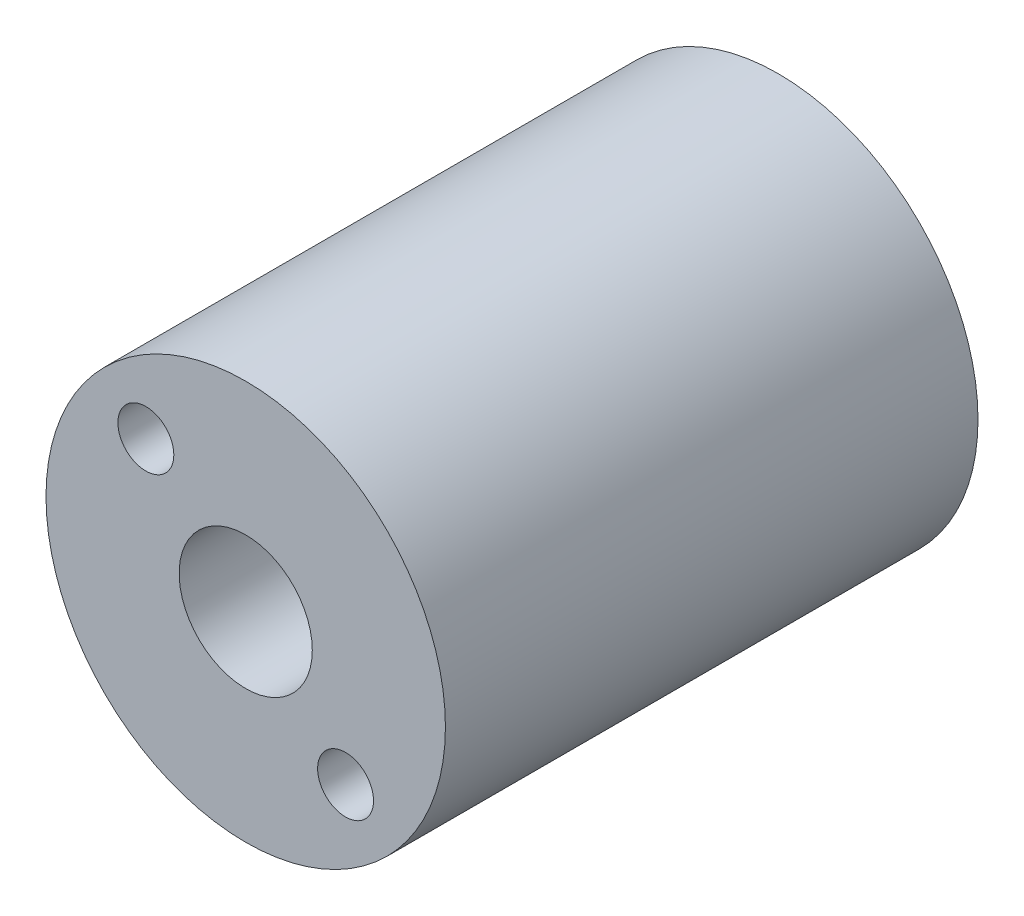
SolidWorks part; units mm, degrees
ref_plane "Ebene vorne" through (0, 0, 0) normal (0, 0, 1) x (1, 0, 0)
ref_plane "Ebene oben" through (0, 0, 0) normal (0, 1, 0) x (1, 0, 0)
ref_plane "Ebene rechts" through (0, 0, 0) normal (1, 0, 0) x (0, 0, -1)
sketch "Skizze1" plane through (0, 0, 0) normal (0, 0, 1) x (1, 0, 0)
  circle A0 centre (0, 0) radius 15
  dimension "D1" = 30
extrude "Aufsatz-Linear austragen1" add sketch "Skizze1" along normal blind 40
sketch "Skizze2" plane through (0, 0, 40) normal (0, 0, 1) x (1, 0, 0)
  circle A0 centre (0, 0) radius 5
  dimension "D1" = 10
extrude "Schnitt-Linear austragen1" cut sketch "Skizze2" against normal through all
hole_wizard "M5 Gewindebohrung1" positions "Skizze7" profile "Skizze8" tap size "M5" standard "DIN" end condition through all
sketch "Skizze7" plane through (0, 0, 40) normal (0, 0, 1) x (1, 0, 0)
  line L0 (0, 0) -> (0, 15.8294) construction
  line L1 (0.1564, 0) -> (20.767, 0) construction
  line L3 (19.9848, -3.4905) -> (20.0239, -3.4905) construction
  point P0 (-7.5, 7.5)
  point P17 (7.5, -7.5)
  dimension "D1" = 7.5
  dimension "D2" = 7.5
  dimension "D3" = 7.5
  dimension "D4" = 7.5
sketch "Skizze8" plane through (-7.5, 7.5, 40) normal (1, 0, 0) x (0, -1, 0)
  line L0 (0, 0) -> (0, 40)
  line L1 (0, 40) -> (2.1, 40)
  line L2 (2.1, 40) -> (2.1, 0)
  line L5 (2.1, 0) -> (0, 0)
  line L11 (0, -6.35) -> (0, 107.95) construction
  dimension "Bohrerdurchmesser" = 4.2
  dimension "Bohrungstiefe" = 40
cosmetic thread "Bohrungsgewinde1" parameters "D2"=5
cosmetic thread "Bohrungsgewinde2" parameters "D2"=5
